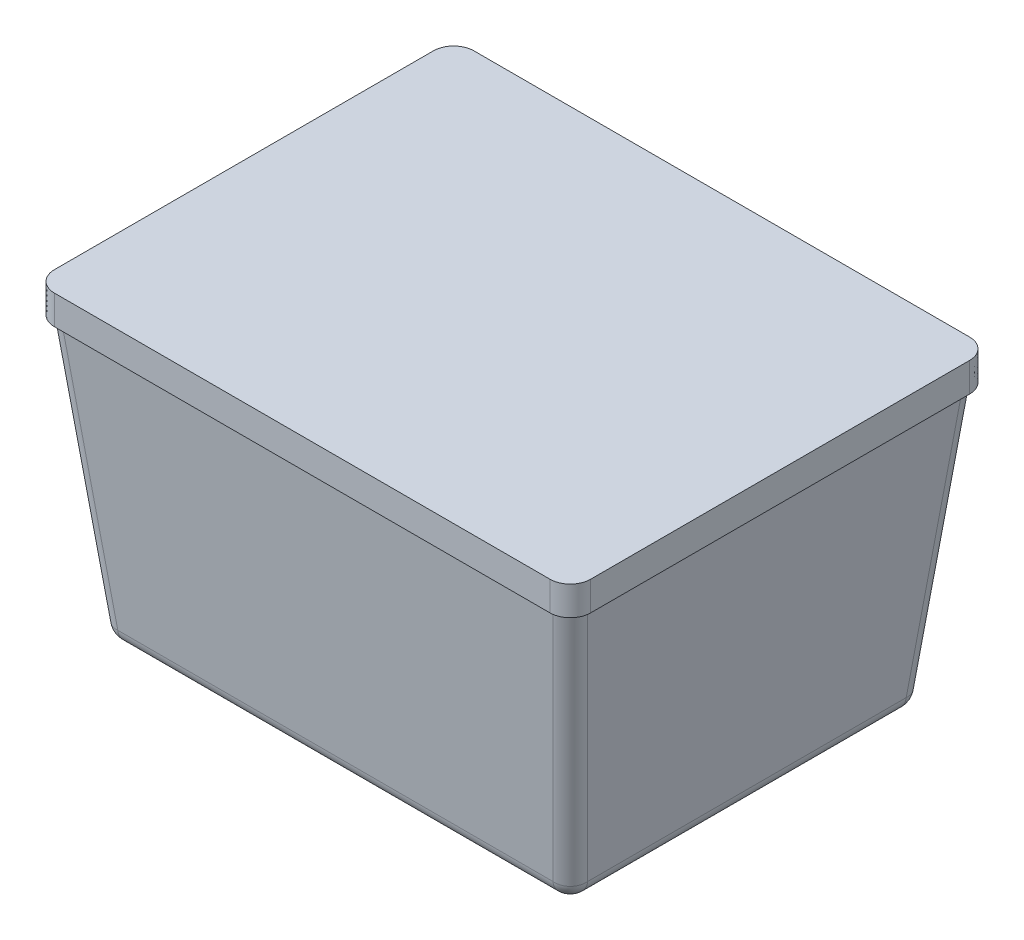
SolidWorks part; units mm, degrees
ref_plane "Alzado" through (0, 0, 0) normal (0, 0, 1) x (1, 0, 0)
ref_plane "Planta" through (0, 0, 0) normal (0, 1, 0) x (1, 0, 0)
ref_plane "Vista lateral" through (0, 0, 0) normal (1, 0, 0) x (0, 0, -1)
sketch "Croquis1" plane through (0, 0, 0) normal (0, 1, 0) x (1, 0, 0)
  line L1 (400, -300) -> (-400, -300)
  line L2 (400, -300) -> (400, 300)
  line L3 (400, 300) -> (-400, 300)
  line L4 (-400, -300) -> (-400, 300)
  line L5 (400, -300) -> (-400, 300) construction
  line L6 (400, 300) -> (-400, -300) construction
  point P0 (0, 0)
  dimension "D1" = 600
  dimension "D2" = 800
extrude "Extruir1" add sketch "Croquis1" along normal blind 520 draft 6 draft outward yes
fillet "Redondeo1" radius 30 8 edges at (0, 0, 300) (400, 0, 0) (0, 0, -300) (-400, 0, 0) (-427.3271, 260, -327.3271) (427.3271, 260, -327.3271) (427.3271, 260, 327.3271) (-427.3271, 260, 327.3271)
shell "Vaciado1" thickness 10 removed face at (0, 520, 0)
sketch "Croquis2" plane through (0, 520, 0) normal (0, 1, 0) x (1, 0, 0)
  line L24 (424.8185, 359.6542) -> (-424.8185, 359.6542)
  line L25 (459.6542, -324.8185) -> (459.6542, 324.8185)
  line L26 (-424.8185, -359.6542) -> (424.8185, -359.6542)
  line L27 (-459.6542, 324.8185) -> (-459.6542, -324.8185)
  line L28 (424.8185, 359.6542) -> (-424.8185, 359.6542)
  line L29 (459.6542, -324.8185) -> (459.6542, 324.8185)
  line L30 (-424.8185, -359.6542) -> (424.8185, -359.6542)
  line L31 (-459.6542, 324.8185) -> (-459.6542, -324.8185)
  spline S0 degree 3 poles (663.0928, -3479.8397) (-47.6648, -298.1304) (-303.9531, 384.1635) (-432.7137, 358.7732) (-433.8149, 358.5002) (-435.4515, 358.0079) (-435.9946, 357.83) (-437.0755, 357.446) (-437.6138, 357.2397) (-440.2615, 356.1489) (-442.2653, 355.0812) (-445.1032, 353.1931) (-446.0209, 352.5157) (-447.3539, 351.425) (-447.7906, 351.0493) (-448.6395, 350.2812) (-449.053, 349.888) (-451.067, 347.8765) (-452.5079, 346.1233) (-454.4118, 343.2761) (-455.0058, 342.2851) (-456.0832, 340.2672) (-456.5688, 339.238) (-457.8704, 336.0912) (-458.5327, 333.9145) (-496.2815, 144.0654) (1020.3325, -196.8187) (3414.6325, -624.2857) knots -7.056418 -7.056418 -7.056418 -7.056418 0.125 0.125 0.1875 0.1875 0.21875 0.21875 0.25 0.25 0.375 0.375 0.4375 0.4375 0.46875 0.46875 0.5 0.5 0.625 0.625 0.6875 0.6875 0.75 0.75 0.875 0.875 11.262721 11.262721 11.262721 11.262721 only from (-424.8185, 359.6542) to (-459.6542, 324.8185)
  spline S1 degree 3 poles (-3379.8397, -763.0928) (-198.1304, -52.3352) (484.1635, 203.9531) (458.7732, 332.7137) (458.5002, 333.8149) (458.0079, 335.4515) (457.83, 335.9946) (457.446, 337.0755) (457.2397, 337.6138) (456.1489, 340.2615) (455.0812, 342.2653) (453.1931, 345.1032) (452.5157, 346.0209) (451.425, 347.3539) (451.0493, 347.7906) (450.2812, 348.6395) (449.888, 349.053) (447.8765, 351.067) (446.1233, 352.5079) (443.2761, 354.4118) (442.2851, 355.0058) (440.2672, 356.0832) (439.238, 356.5688) (436.0912, 357.8704) (433.9145, 358.5327) (244.0654, 396.2815) (-96.8187, -1120.3325) (-524.2857, -3514.6325) knots -7.056418 -7.056418 -7.056418 -7.056418 0.125 0.125 0.1875 0.1875 0.21875 0.21875 0.25 0.25 0.375 0.375 0.4375 0.4375 0.46875 0.46875 0.5 0.5 0.625 0.625 0.6875 0.6875 0.75 0.75 0.875 0.875 11.262721 11.262721 11.262721 11.262721 only from (459.6542, 324.8185) to (424.8185, 359.6542)
  spline S2 degree 3 poles (-663.0928, 3479.8397) (47.6648, 298.1304) (303.9531, -384.1635) (432.7137, -358.7732) (433.8149, -358.5002) (435.4515, -358.0079) (435.9946, -357.83) (437.0755, -357.446) (437.6138, -357.2397) (440.2615, -356.1489) (442.2653, -355.0812) (445.1032, -353.1931) (446.0209, -352.5157) (447.3539, -351.425) (447.7906, -351.0493) (448.6395, -350.2812) (449.053, -349.888) (451.067, -347.8765) (452.5079, -346.1233) (454.4118, -343.2761) (455.0058, -342.2851) (456.0832, -340.2672) (456.5688, -339.238) (457.8704, -336.0912) (458.5327, -333.9145) (496.2815, -144.0654) (-1020.3325, 196.8187) (-3414.6325, 624.2857) knots -7.056418 -7.056418 -7.056418 -7.056418 0.125 0.125 0.1875 0.1875 0.21875 0.21875 0.25 0.25 0.375 0.375 0.4375 0.4375 0.46875 0.46875 0.5 0.5 0.625 0.625 0.6875 0.6875 0.75 0.75 0.875 0.875 11.262721 11.262721 11.262721 11.262721 only from (424.8185, -359.6542) to (459.6542, -324.8185)
  spline S3 degree 3 poles (3379.8397, 763.0928) (198.1304, 52.3352) (-484.1635, -203.9531) (-458.7732, -332.7137) (-458.5002, -333.8149) (-458.0079, -335.4515) (-457.83, -335.9946) (-457.446, -337.0755) (-457.2397, -337.6138) (-456.1489, -340.2615) (-455.0812, -342.2653) (-453.1931, -345.1032) (-452.5157, -346.0209) (-451.425, -347.3539) (-451.0493, -347.7906) (-450.2812, -348.6395) (-449.888, -349.053) (-447.8765, -351.067) (-446.1233, -352.5079) (-443.2761, -354.4118) (-442.2851, -355.0058) (-440.2672, -356.0832) (-439.238, -356.5688) (-436.0912, -357.8704) (-433.9145, -358.5327) (-244.0654, -396.2815) (96.8187, 1120.3325) (524.2857, 3514.6325) knots -7.056418 -7.056418 -7.056418 -7.056418 0.125 0.125 0.1875 0.1875 0.21875 0.21875 0.25 0.25 0.375 0.375 0.4375 0.4375 0.46875 0.46875 0.5 0.5 0.625 0.625 0.6875 0.6875 0.75 0.75 0.875 0.875 11.262721 11.262721 11.262721 11.262721 only from (-459.6542, -324.8185) to (-424.8185, -359.6542)
  spline S4 degree 3 poles (-424.8185, 359.6542) (-427.1201, 359.6542) (-429.3809, 359.4304) (-432.7137, 358.7732) (-433.8149, 358.5002) (-435.4515, 358.0079) (-435.9946, 357.83) (-437.0755, 357.446) (-437.6138, 357.2397) (-440.2615, 356.1489) (-442.2653, 355.0812) (-445.1032, 353.1931) (-446.0209, 352.5157) (-447.3539, 351.425) (-447.7906, 351.0493) (-448.6395, 350.2812) (-449.053, 349.888) (-451.067, 347.8765) (-452.5079, 346.1233) (-454.4118, 343.2761) (-455.0058, 342.2851) (-456.0832, 340.2672) (-456.5688, 339.238) (-457.8704, 336.0912) (-458.5327, 333.9145) (-459.4304, 329.3998) (-459.6542, 327.1202) (-459.6542, 324.8185) knots 0 0 0 0 0.125 0.125 0.1875 0.1875 0.21875 0.21875 0.25 0.25 0.375 0.375 0.4375 0.4375 0.46875 0.46875 0.5 0.5 0.625 0.625 0.6875 0.6875 0.75 0.75 0.875 0.875 1 1 1 1
  spline S5 degree 3 poles (459.6542, 324.8185) (459.6542, 327.1201) (459.4304, 329.3809) (458.7732, 332.7137) (458.5002, 333.8149) (458.0079, 335.4515) (457.83, 335.9946) (457.446, 337.0755) (457.2397, 337.6138) (456.1489, 340.2615) (455.0812, 342.2653) (453.1931, 345.1032) (452.5157, 346.0209) (451.425, 347.3539) (451.0493, 347.7906) (450.2812, 348.6395) (449.888, 349.053) (447.8765, 351.067) (446.1233, 352.5079) (443.2761, 354.4118) (442.2851, 355.0058) (440.2672, 356.0832) (439.238, 356.5688) (436.0912, 357.8704) (433.9145, 358.5327) (429.3998, 359.4304) (427.1202, 359.6542) (424.8185, 359.6542) knots 0 0 0 0 0.125 0.125 0.1875 0.1875 0.21875 0.21875 0.25 0.25 0.375 0.375 0.4375 0.4375 0.46875 0.46875 0.5 0.5 0.625 0.625 0.6875 0.6875 0.75 0.75 0.875 0.875 1 1 1 1
  spline S6 degree 3 poles (424.8185, -359.6542) (427.1201, -359.6542) (429.3809, -359.4304) (432.7137, -358.7732) (433.8149, -358.5002) (435.4515, -358.0079) (435.9946, -357.83) (437.0755, -357.446) (437.6138, -357.2397) (440.2615, -356.1489) (442.2653, -355.0812) (445.1032, -353.1931) (446.0209, -352.5157) (447.3539, -351.425) (447.7906, -351.0493) (448.6395, -350.2812) (449.053, -349.888) (451.067, -347.8765) (452.5079, -346.1233) (454.4118, -343.2761) (455.0058, -342.2851) (456.0832, -340.2672) (456.5688, -339.238) (457.8704, -336.0912) (458.5327, -333.9145) (459.4304, -329.3998) (459.6542, -327.1202) (459.6542, -324.8185) knots 0 0 0 0 0.125 0.125 0.1875 0.1875 0.21875 0.21875 0.25 0.25 0.375 0.375 0.4375 0.4375 0.46875 0.46875 0.5 0.5 0.625 0.625 0.6875 0.6875 0.75 0.75 0.875 0.875 1 1 1 1
  spline S7 degree 3 poles (-459.6542, -324.8185) (-459.6542, -327.1201) (-459.4304, -329.3809) (-458.7732, -332.7137) (-458.5002, -333.8149) (-458.0079, -335.4515) (-457.83, -335.9946) (-457.446, -337.0755) (-457.2397, -337.6138) (-456.1489, -340.2615) (-455.0812, -342.2653) (-453.1931, -345.1032) (-452.5157, -346.0209) (-451.425, -347.3539) (-451.0493, -347.7906) (-450.2812, -348.6395) (-449.888, -349.053) (-447.8765, -351.067) (-446.1233, -352.5079) (-443.2761, -354.4118) (-442.2851, -355.0058) (-440.2672, -356.0832) (-439.238, -356.5688) (-436.0912, -357.8704) (-433.9145, -358.5327) (-429.3998, -359.4304) (-427.1202, -359.6542) (-424.8185, -359.6542) knots 0 0 0 0 0.125 0.125 0.1875 0.1875 0.21875 0.21875 0.25 0.25 0.375 0.375 0.4375 0.4375 0.46875 0.46875 0.5 0.5 0.625 0.625 0.6875 0.6875 0.75 0.75 0.875 0.875 1 1 1 1
  dimension "D1" = 5
extrude "Extruir2" add sketch "Croquis2" against normal blind 40 separate body
sketch "Croquis3" plane through (0, 520, 0) normal (0, 1, 0) x (1, 0, 0)
  line L4 (-459.6542, 324.8185) -> (-459.6542, -324.8185)
  line L5 (-424.8185, -359.6542) -> (424.8185, -359.6542)
  line L6 (459.6542, -324.8185) -> (459.6542, 324.8185)
  line L7 (424.8185, 359.6542) -> (-424.8185, 359.6542)
  line L8 (-459.6542, 324.8185) -> (-459.6542, -324.8185)
  line L9 (-424.8185, -359.6542) -> (424.8185, -359.6542)
  line L10 (459.6542, -324.8185) -> (459.6542, 324.8185)
  line L11 (424.8185, 359.6542) -> (-424.8185, 359.6542)
  spline S4 degree 3 poles (663.0928, -3479.8397) (-47.6648, -298.1304) (-303.9531, 384.1635) (-432.7137, 358.7732) (-433.8149, 358.5002) (-435.4515, 358.0079) (-435.9946, 357.83) (-437.0755, 357.446) (-437.6138, 357.2397) (-440.2615, 356.1489) (-442.2653, 355.0812) (-445.1032, 353.1931) (-446.0209, 352.5157) (-447.3539, 351.425) (-447.7906, 351.0493) (-448.6395, 350.2812) (-449.053, 349.888) (-451.067, 347.8765) (-452.5079, 346.1233) (-454.4118, 343.2761) (-455.0058, 342.2851) (-456.0832, 340.2672) (-456.5688, 339.238) (-457.8704, 336.0912) (-458.5327, 333.9145) (-496.2815, 144.0654) (1020.3325, -196.8187) (3414.6325, -624.2857) knots -7.056418 -7.056418 -7.056418 -7.056418 0.125 0.125 0.1875 0.1875 0.21875 0.21875 0.25 0.25 0.375 0.375 0.4375 0.4375 0.46875 0.46875 0.5 0.5 0.625 0.625 0.6875 0.6875 0.75 0.75 0.875 0.875 11.262721 11.262721 11.262721 11.262721 only from (-424.8185, 359.6542) to (-459.6542, 324.8185)
  spline S5 degree 3 poles (3379.8397, 763.0928) (198.1304, 52.3352) (-484.1635, -203.9531) (-458.7732, -332.7137) (-458.5002, -333.8149) (-458.0079, -335.4515) (-457.83, -335.9946) (-457.446, -337.0755) (-457.2397, -337.6138) (-456.1489, -340.2615) (-455.0812, -342.2653) (-453.1931, -345.1032) (-452.5157, -346.0209) (-451.425, -347.3539) (-451.0493, -347.7906) (-450.2812, -348.6395) (-449.888, -349.053) (-447.8765, -351.067) (-446.1233, -352.5079) (-443.2761, -354.4118) (-442.2851, -355.0058) (-440.2672, -356.0832) (-439.238, -356.5688) (-436.0912, -357.8704) (-433.9145, -358.5327) (-244.0654, -396.2815) (96.8187, 1120.3325) (524.2857, 3514.6325) knots -7.056418 -7.056418 -7.056418 -7.056418 0.125 0.125 0.1875 0.1875 0.21875 0.21875 0.25 0.25 0.375 0.375 0.4375 0.4375 0.46875 0.46875 0.5 0.5 0.625 0.625 0.6875 0.6875 0.75 0.75 0.875 0.875 11.262721 11.262721 11.262721 11.262721 only from (-459.6542, -324.8185) to (-424.8185, -359.6542)
  spline S6 degree 3 poles (-663.0928, 3479.8397) (47.6648, 298.1304) (303.9531, -384.1635) (432.7137, -358.7732) (433.8149, -358.5002) (435.4515, -358.0079) (435.9946, -357.83) (437.0755, -357.446) (437.6138, -357.2397) (440.2615, -356.1489) (442.2653, -355.0812) (445.1032, -353.1931) (446.0209, -352.5157) (447.3539, -351.425) (447.7906, -351.0493) (448.6395, -350.2812) (449.053, -349.888) (451.067, -347.8765) (452.5079, -346.1233) (454.4118, -343.2761) (455.0058, -342.2851) (456.0832, -340.2672) (456.5688, -339.238) (457.8704, -336.0912) (458.5327, -333.9145) (496.2815, -144.0654) (-1020.3325, 196.8187) (-3414.6325, 624.2857) knots -7.056418 -7.056418 -7.056418 -7.056418 0.125 0.125 0.1875 0.1875 0.21875 0.21875 0.25 0.25 0.375 0.375 0.4375 0.4375 0.46875 0.46875 0.5 0.5 0.625 0.625 0.6875 0.6875 0.75 0.75 0.875 0.875 11.262721 11.262721 11.262721 11.262721 only from (424.8185, -359.6542) to (459.6542, -324.8185)
  spline S7 degree 3 poles (-3379.8397, -763.0928) (-198.1304, -52.3352) (484.1635, 203.9531) (458.7732, 332.7137) (458.5002, 333.8149) (458.0079, 335.4515) (457.83, 335.9946) (457.446, 337.0755) (457.2397, 337.6138) (456.1489, 340.2615) (455.0812, 342.2653) (453.1931, 345.1032) (452.5157, 346.0209) (451.425, 347.3539) (451.0493, 347.7906) (450.2812, 348.6395) (449.888, 349.053) (447.8765, 351.067) (446.1233, 352.5079) (443.2761, 354.4118) (442.2851, 355.0058) (440.2672, 356.0832) (439.238, 356.5688) (436.0912, 357.8704) (433.9145, 358.5327) (244.0654, 396.2815) (-96.8187, -1120.3325) (-524.2857, -3514.6325) knots -7.056418 -7.056418 -7.056418 -7.056418 0.125 0.125 0.1875 0.1875 0.21875 0.21875 0.25 0.25 0.375 0.375 0.4375 0.4375 0.46875 0.46875 0.5 0.5 0.625 0.625 0.6875 0.6875 0.75 0.75 0.875 0.875 11.262721 11.262721 11.262721 11.262721 only from (459.6542, 324.8185) to (424.8185, 359.6542)
  spline S8 degree 3 poles (-424.8185, 359.6542) (-427.1201, 359.6542) (-429.3809, 359.4304) (-432.7137, 358.7732) (-433.8149, 358.5002) (-435.4515, 358.0079) (-435.9946, 357.83) (-437.0755, 357.446) (-437.6138, 357.2397) (-440.2615, 356.1489) (-442.2653, 355.0812) (-445.1032, 353.1931) (-446.0209, 352.5157) (-447.3539, 351.425) (-447.7906, 351.0493) (-448.6395, 350.2812) (-449.053, 349.888) (-451.067, 347.8765) (-452.5079, 346.1233) (-454.4118, 343.2761) (-455.0058, 342.2851) (-456.0832, 340.2672) (-456.5688, 339.238) (-457.8704, 336.0912) (-458.5327, 333.9145) (-459.4304, 329.3998) (-459.6542, 327.1202) (-459.6542, 324.8185) knots 0 0 0 0 0.125 0.125 0.1875 0.1875 0.21875 0.21875 0.25 0.25 0.375 0.375 0.4375 0.4375 0.46875 0.46875 0.5 0.5 0.625 0.625 0.6875 0.6875 0.75 0.75 0.875 0.875 1 1 1 1
  spline S9 degree 3 poles (-459.6542, -324.8185) (-459.6542, -327.1201) (-459.4304, -329.3809) (-458.7732, -332.7137) (-458.5002, -333.8149) (-458.0079, -335.4515) (-457.83, -335.9946) (-457.446, -337.0755) (-457.2397, -337.6138) (-456.1489, -340.2615) (-455.0812, -342.2653) (-453.1931, -345.1032) (-452.5157, -346.0209) (-451.425, -347.3539) (-451.0493, -347.7906) (-450.2812, -348.6395) (-449.888, -349.053) (-447.8765, -351.067) (-446.1233, -352.5079) (-443.2761, -354.4118) (-442.2851, -355.0058) (-440.2672, -356.0832) (-439.238, -356.5688) (-436.0912, -357.8704) (-433.9145, -358.5327) (-429.3998, -359.4304) (-427.1202, -359.6542) (-424.8185, -359.6542) knots 0 0 0 0 0.125 0.125 0.1875 0.1875 0.21875 0.21875 0.25 0.25 0.375 0.375 0.4375 0.4375 0.46875 0.46875 0.5 0.5 0.625 0.625 0.6875 0.6875 0.75 0.75 0.875 0.875 1 1 1 1
  spline S10 degree 3 poles (424.8185, -359.6542) (427.1201, -359.6542) (429.3809, -359.4304) (432.7137, -358.7732) (433.8149, -358.5002) (435.4515, -358.0079) (435.9946, -357.83) (437.0755, -357.446) (437.6138, -357.2397) (440.2615, -356.1489) (442.2653, -355.0812) (445.1032, -353.1931) (446.0209, -352.5157) (447.3539, -351.425) (447.7906, -351.0493) (448.6395, -350.2812) (449.053, -349.888) (451.067, -347.8765) (452.5079, -346.1233) (454.4118, -343.2761) (455.0058, -342.2851) (456.0832, -340.2672) (456.5688, -339.238) (457.8704, -336.0912) (458.5327, -333.9145) (459.4304, -329.3998) (459.6542, -327.1202) (459.6542, -324.8185) knots 0 0 0 0 0.125 0.125 0.1875 0.1875 0.21875 0.21875 0.25 0.25 0.375 0.375 0.4375 0.4375 0.46875 0.46875 0.5 0.5 0.625 0.625 0.6875 0.6875 0.75 0.75 0.875 0.875 1 1 1 1
  spline S11 degree 3 poles (459.6542, 324.8185) (459.6542, 327.1201) (459.4304, 329.3809) (458.7732, 332.7137) (458.5002, 333.8149) (458.0079, 335.4515) (457.83, 335.9946) (457.446, 337.0755) (457.2397, 337.6138) (456.1489, 340.2615) (455.0812, 342.2653) (453.1931, 345.1032) (452.5157, 346.0209) (451.425, 347.3539) (451.0493, 347.7906) (450.2812, 348.6395) (449.888, 349.053) (447.8765, 351.067) (446.1233, 352.5079) (443.2761, 354.4118) (442.2851, 355.0058) (440.2672, 356.0832) (439.238, 356.5688) (436.0912, 357.8704) (433.9145, 358.5327) (429.3998, 359.4304) (427.1202, 359.6542) (424.8185, 359.6542) knots 0 0 0 0 0.125 0.125 0.1875 0.1875 0.21875 0.21875 0.25 0.25 0.375 0.375 0.4375 0.4375 0.46875 0.46875 0.5 0.5 0.625 0.625 0.6875 0.6875 0.75 0.75 0.875 0.875 1 1 1 1
  dimension "D1" = 0
extrude "Extruir3" add sketch "Croquis3" along normal blind 10
